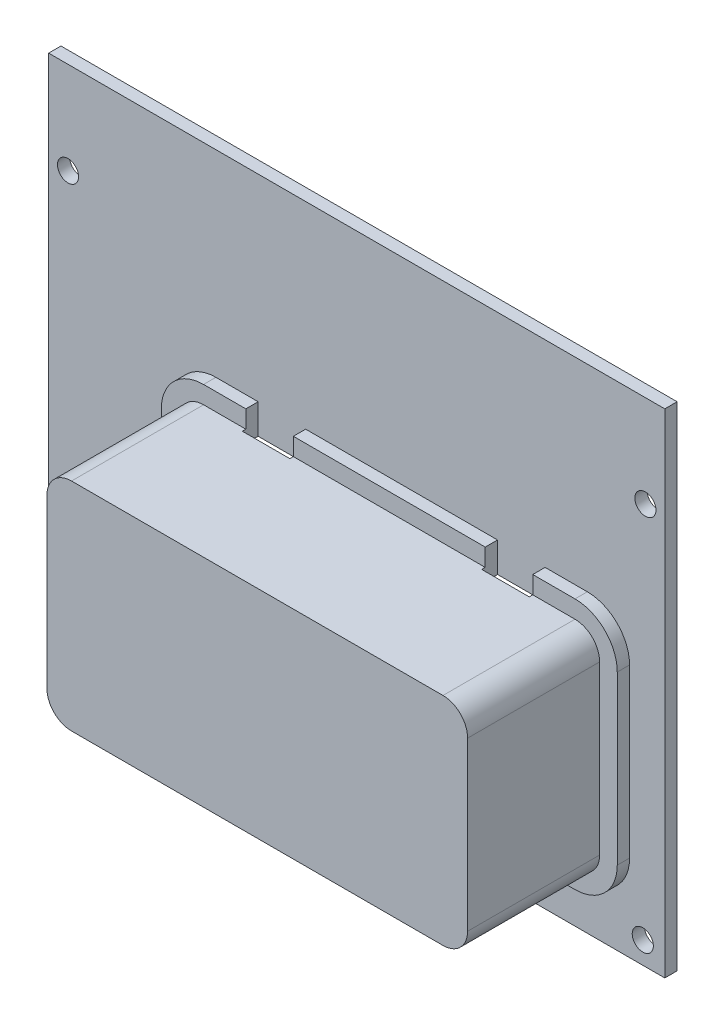
SolidWorks part; units mm, degrees
ref_plane "Front Plane" through (0, 0, 0) normal (0, 0, 1) x (1, 0, 0)
ref_plane "Top Plane" through (0, 0, 0) normal (0, 1, 0) x (1, 0, 0)
ref_plane "Right Plane" through (0, 0, 0) normal (1, 0, 0) x (0, 0, -1)
sketch "Sketch1" plane through (0, 0, 0) normal (0, 0, 1) x (1, 0, 0)
  line L1 (-44.45, 35.56) -> (44.45, 35.56)
  line L2 (-44.45, 35.56) -> (-44.45, -35.56)
  line L3 (-44.45, -35.56) -> (44.45, -35.56)
  line L4 (44.45, 35.56) -> (44.45, -35.56)
  line L5 (-44.45, 35.56) -> (44.45, -35.56) construction
  line L6 (-44.45, -35.56) -> (44.45, 35.56) construction
  point P0 (0, 0)
  dimension "D1" = 71.12
  dimension "D2" = 88.9
extrude "Boss-Extrude1" add sketch "Sketch1" along normal blind 1.778
sketch "Sketch2" plane through (0, 0, 0) normal (0, 0, -1) x (-1, 0, 0)
  line L0 (0, 0) -> (0, 20.9387) construction
  circle A5 centre (-41.656, 22.2581) radius 1.524
  circle A6 centre (-41.275, -32.385) radius 1.524
  circle A7 centre (41.275, -32.385) radius 1.524
  circle A8 centre (41.656, 22.2581) radius 1.524
  dimension "D1" = 3.048
  dimension "D2" = 3.048
sketch "Sketch3" plane through (0, 0, 1.778) normal (0, 0, 1) x (1, 0, 0)
  line L0 (-22.098, 1.016) -> (-22.098, -23.114)
  line L5 (-20.32, -24.892) -> (33.274, -24.892)
  line L6 (35.052, 1.016) -> (35.052, -23.114)
  line L7 (-20.32, 2.794) -> (33.274, 2.794)
  line L12 (-20.32, 4.572) -> (33.274, 4.572)
  line L13 (-23.876, 1.016) -> (-23.876, -23.114)
  line L14 (-20.32, -26.67) -> (33.274, -26.67)
  line L15 (36.83, 1.016) -> (36.83, -23.114)
  line L16 (-44.45, -35.56) -> (44.45, -35.56) construction
  arc A4 (-22.098, -23.114) -> (-20.32, -24.892) centre (-20.32, -23.114) ccw
  arc A5 (33.274, -24.892) -> (35.052, -23.114) centre (33.274, -23.114) ccw
  arc A6 (35.052, 1.016) -> (33.274, 2.794) centre (33.274, 1.016) ccw
  arc A7 (-22.098, 1.016) -> (-20.32, 2.794) centre (-20.32, 1.016) cw
  arc A8 (36.83, 1.016) -> (33.274, 4.572) centre (33.274, 1.016) ccw
  arc A9 (-23.876, 1.016) -> (-20.32, 4.572) centre (-20.32, 1.016) cw
  arc A10 (-23.876, -23.114) -> (-20.32, -26.67) centre (-20.32, -23.114) ccw
  arc A11 (33.274, -26.67) -> (36.83, -23.114) centre (33.274, -23.114) ccw
  dimension "D3" = 8.89
  dimension "D1" = 57.15
  dimension "D2" = 1.778
extrude "Boss-Extrude2" add sketch "Sketch3" along normal blind 19.05
extrude "Cut-Extrude8" cut sketch "Sketch2" against normal blind 1.778
sketch "Sketch17" plane through (0, 0, 20.828) normal (0, 0, 1) x (1, 0, 0)
  line L0 (33.274, -26.67) -> (-20.32, -26.67)
  line L6 (-23.876, -23.114) -> (-23.876, 1.016)
  line L8 (-20.32, 4.572) -> (33.274, 4.572)
  line L10 (36.83, 1.016) -> (36.83, -23.114)
  arc A0 (36.83, -23.114) -> (33.274, -26.67) centre (33.274, -23.114) cw
  arc A1 (-20.32, -26.67) -> (-23.876, -23.114) centre (-20.32, -23.114) cw
  arc A2 (-23.876, 1.016) -> (-20.32, 4.572) centre (-20.32, 1.016) cw
  arc A3 (36.83, 1.016) -> (33.274, 4.572) centre (33.274, 1.016) ccw
extrude "Boss-Extrude8" add sketch "Sketch17" along normal blind 1.778
sketch "Sketch18" plane through (0, 4.572, 0) normal (0, 1, 0) x (1, 0, 0)
  line L0 (6.477, -20.828) -> (6.477, -6.7383) construction
  line L1 (33.274, -20.828) -> (-20.32, -20.828) construction
  line L2 (44.45, -1.778) -> (-44.45, -1.778) construction
  line L3 (-14.224, -1.778) -> (-7.366, -1.778)
  line L4 (-14.224, -1.778) -> (-14.224, -4.064)
  line L5 (-14.224, -4.064) -> (-7.366, -4.064)
  line L6 (-7.366, -1.778) -> (-7.366, -4.064)
  line L7 (-20.32, -22.606) -> (-20.32, -1.778) construction
  line L8 (27.178, -4.064) -> (20.32, -4.064)
  line L9 (20.32, -1.778) -> (20.32, -4.064)
  line L10 (27.178, -1.778) -> (20.32, -1.778)
  line L11 (27.178, -1.778) -> (27.178, -4.064)
  line L12 (33.274, -22.606) -> (33.274, -1.778) construction
  dimension "D1" = 2.286
  dimension "D2" = 6.858
  dimension "D3" = 6.096
extrude "Cut-Extrude9" cut sketch "Sketch18" against normal blind 1.778
sketch "Sketch19" plane through (0, 0, 0) normal (0, 0, -1) x (-1, 0, 0)
  line L0 (44.45, -35.56) -> (-44.45, -35.56) construction
  line L1 (-33.274, 2.794) -> (20.32, 2.794)
  line L2 (-35.052, 1.016) -> (-35.052, -23.114)
  line L3 (-33.274, -24.892) -> (20.32, -24.892)
  line L4 (22.098, 1.016) -> (22.098, -23.114)
  line L5 (-20.32, 2.794) -> (7.366, 2.794) construction
  arc A0 (20.32, 2.794) -> (22.098, 1.016) centre (20.32, 1.016) cw
  arc A1 (20.32, -24.892) -> (22.098, -23.114) centre (20.32, -23.114) ccw
  arc A2 (-35.052, -23.114) -> (-33.274, -24.892) centre (-33.274, -23.114) ccw
  arc A3 (-33.274, 2.794) -> (-35.052, 1.016) centre (-33.274, 1.016) ccw
  dimension "D1" = 1.778
  dimension "D2" = 10.668
extrude "Cut-Extrude20" cut sketch "Sketch19" against normal blind 1.778
sketch "Sketch20" plane through (-23.876, 0, 0) normal (-1, 0, 0) x (0, 0, 1)
  line L8 (20.828, 1.016) -> (20.828, -23.114) construction
  line L13 (20.828, -6.604) -> (5.588, -6.604)
  line L14 (20.828, -6.604) -> (20.828, -15.494)
  line L15 (20.828, -15.494) -> (5.588, -15.494)
  line L16 (5.588, -6.604) -> (5.588, -15.494)
  line L17 (22.606, -23.114) -> (1.778, -23.114) construction
  line L18 (22.606, 1.016) -> (1.778, 1.016) construction
  line L19 (1.778, 35.56) -> (1.778, -35.56) construction
  dimension "D1" = 7.62
  dimension "D2" = 7.62
  dimension "D3" = 3.81
sketch "Sketch30" plane through (0, 0, 1.778) normal (0, 0, 1) x (1, 0, 0)
  line L4 (-14.224, 4.572) -> (-14.224, 7.112)
  line L5 (-7.366, 4.572) -> (-7.366, 7.112)
  line L6 (20.32, 4.572) -> (20.32, 7.112)
  line L7 (27.178, 4.572) -> (27.178, 7.112)
  line L8 (-26.416, 1.016) -> (-26.416, -23.114)
  line L9 (-20.32, -29.21) -> (33.274, -29.21)
  line L10 (39.37, -23.114) -> (39.37, 1.016)
  line L11 (33.274, 7.112) -> (-20.32, 7.112)
  line L12 (-26.416, 1.016) -> (-26.416, -23.114)
  line L13 (-20.32, -29.21) -> (33.274, -29.21)
  line L14 (39.37, -23.114) -> (39.37, 1.016)
  line L15 (33.274, 7.112) -> (27.178, 7.112)
  line L16 (-14.224, 7.112) -> (-20.32, 7.112)
  line L17 (20.32, 7.112) -> (-7.366, 7.112)
  line L18 (-14.224, 4.572) -> (-20.32, 4.572)
  line L20 (-23.876, 1.016) -> (-23.876, -23.114)
  line L22 (-20.32, -26.67) -> (33.274, -26.67)
  line L24 (36.83, -23.114) -> (36.83, 1.016)
  line L26 (33.274, 4.572) -> (27.178, 4.572)
  line L28 (-7.366, 7.112) -> (20.32, 7.112)
  line L29 (-7.366, 7.112) -> (-7.366, 4.572)
  line L30 (-7.366, 4.572) -> (20.32, 4.572)
  line L31 (20.32, 7.112) -> (20.32, 4.572)
  arc A4 (-20.32, 4.572) -> (-23.876, 1.016) centre (-20.32, 1.016) ccw
  arc A5 (-23.876, -23.114) -> (-20.32, -26.67) centre (-20.32, -23.114) ccw
  arc A6 (33.274, -26.67) -> (36.83, -23.114) centre (33.274, -23.114) ccw
  arc A7 (36.83, 1.016) -> (33.274, 4.572) centre (33.274, 1.016) ccw
  arc A8 (-26.416, -23.114) -> (-20.32, -29.21) centre (-20.32, -23.114) ccw
  arc A9 (33.274, -29.21) -> (39.37, -23.114) centre (33.274, -23.114) ccw
  arc A10 (39.37, 1.016) -> (33.274, 7.112) centre (33.274, 1.016) ccw
  arc A11 (-20.32, 7.112) -> (-26.416, 1.016) centre (-20.32, 1.016) ccw
  arc A12 (-26.416, -23.114) -> (-20.32, -29.21) centre (-20.32, -23.114) ccw
  arc A13 (33.274, -29.21) -> (39.37, -23.114) centre (33.274, -23.114) ccw
  arc A14 (39.37, 1.016) -> (33.274, 7.112) centre (33.274, 1.016) ccw
  arc A15 (-20.32, 7.112) -> (-26.416, 1.016) centre (-20.32, 1.016) ccw
  line M15 (27.178, 4.572) -> (33.274, 4.572)
  arc M16 (33.274, 4.572) -> (36.83, 1.016) centre (33.274, 1.016) cw
  line M17 (36.83, 1.016) -> (36.83, -23.114)
  arc M18 (36.83, -23.114) -> (33.274, -26.67) centre (33.274, -23.114) cw
  line M19 (33.274, -26.67) -> (-20.32, -26.67)
  arc M20 (-20.32, -26.67) -> (-23.876, -23.114) centre (-20.32, -23.114) cw
  line M21 (-23.876, -23.114) -> (-23.876, 1.016)
  arc M22 (-23.876, 1.016) -> (-20.32, 4.572) centre (-20.32, 1.016) cw
  line M23 (-20.32, 4.572) -> (-14.224, 4.572)
  line M27 (-7.366, 4.572) -> (20.32, 4.572)
  dimension "D1" = 2.54
extrude "Boss-Extrude18" add sketch "Sketch30" along normal blind 1.778 contours L16 A15 L12 A12 L13 A13 L14 A14 L15 L7 L4 M15 M16 M17 M18 M19 M20 M21 M22 M23 | L6 L17 L5 M27 region at (-17.272, 5.3235, 1.778) region at (6.477, 5.842, 1.778)
sketch "Sketch32" plane through (0, 0, 0) normal (0, 0, -1) x (-1, 0, 0)
  line L2 (-33.274, -24.892) -> (20.32, -24.892) construction
  line L6 (-35.052, 1.016) -> (-35.052, -23.114)
  line L7 (-33.274, -24.892) -> (20.32, -24.892)
  line L8 (22.098, -23.114) -> (22.098, 1.016)
  line L9 (23.876, -23.114) -> (23.876, 1.016)
  line L10 (-33.274, -26.67) -> (20.32, -26.67)
  line L11 (-36.83, 1.016) -> (-36.83, -23.114)
  line L12 (23.876, -23.114) -> (23.876, 1.016)
  line L13 (-33.274, -26.67) -> (-10.541, -26.67)
  line L14 (-36.83, 1.016) -> (-36.83, -23.114)
  line L15 (-36.83, 1.016) -> (-35.052, 1.016)
  line L16 (22.098, 1.016) -> (23.876, 1.016)
  line L17 (-2.413, -26.67) -> (20.32, -26.67)
  line L18 (-33.274, -26.67) -> (20.32, -26.67) construction
  arc A0 (-10.541, -26.67) -> (-2.413, -26.67) centre (-6.477, -26.67) ccw
  arc A6 (-35.052, -23.114) -> (-33.274, -24.892) centre (-33.274, -23.114) ccw
  arc A7 (20.32, -24.892) -> (22.098, -23.114) centre (20.32, -23.114) ccw
  arc A9 (23.876, 1.016) -> (20.32, 4.572) centre (20.32, 1.016) ccw
  arc A10 (20.32, -26.67) -> (23.876, -23.114) centre (20.32, -23.114) ccw
  arc A11 (-36.83, -23.114) -> (-33.274, -26.67) centre (-33.274, -23.114) ccw
  arc A12 (-33.274, 4.572) -> (-36.83, 1.016) centre (-33.274, 1.016) ccw
  arc A14 (20.32, -26.67) -> (23.876, -23.114) centre (20.32, -23.114) ccw
  arc A15 (-36.83, -23.114) -> (-33.274, -26.67) centre (-33.274, -23.114) ccw
  arc A17 (-33.274, 4.572) -> (-36.83, 1.016) centre (-33.274, 1.016) ccw construction
  arc A18 (-33.274, 2.794) -> (-35.052, 1.016) centre (-33.274, 1.016) ccw construction
  arc A19 (22.098, 1.016) -> (20.32, 2.794) centre (20.32, 1.016) ccw construction
  arc A20 (23.876, 1.016) -> (20.32, 4.572) centre (20.32, 1.016) ccw construction
  point P7 (-6.477, -24.892)
  dimension "D1" = 8.128
  dimension "D2" = 1.778
  dimension "D3" = 1.778
  dimension "D4" = 1.778
sketch "Sketch33" plane through (0, 0, 0) normal (0, 0, -1) x (-1, 0, 0)
  line L0 (-12.319, -26.67) -> (-0.635, -26.67)
  arc A2 (-12.319, -26.67) -> (-0.635, -26.67) centre (-6.477, -26.67) ccw
  arc A3 (-12.319, -26.67) -> (-0.635, -26.67) centre (-6.477, -26.67) ccw
  dimension "D1" = 1.778
extrude "Boss-Extrude20" add sketch "Sketch33" against normal blind 8.89
extrude "Cut-Extrude21" cut sketch "Sketch32" against normal blind 2.032
extrude "Cut-Extrude22" cut sketch "Sketch20" against normal blind 1.778
sketch "Sketch34" plane through (0, 0, 2.032) normal (0, 0, -1) x (-1, 0, 0)
  line L0 (20.32, -24.892) -> (-33.274, -24.892) construction
  circle A0 centre (-6.477, -27.813) radius 1.27
  dimension "D1" = 2.54
  dimension "D2" = 2.921
extrude "Cut-Extrude23" cut sketch "Sketch34" against normal blind 3.81
sketch "Sketch35" plane through (0, 0, 0) normal (0, 0, -1) x (-1, 0, 0)
  text T0 "Naxis Inc." font "Consolas" height 3.175
  text T1 "Made in USA" font "Consolas" height in points 8
extrude "Cut-Extrude24" cut sketch "Sketch35" against normal blind 0.254
